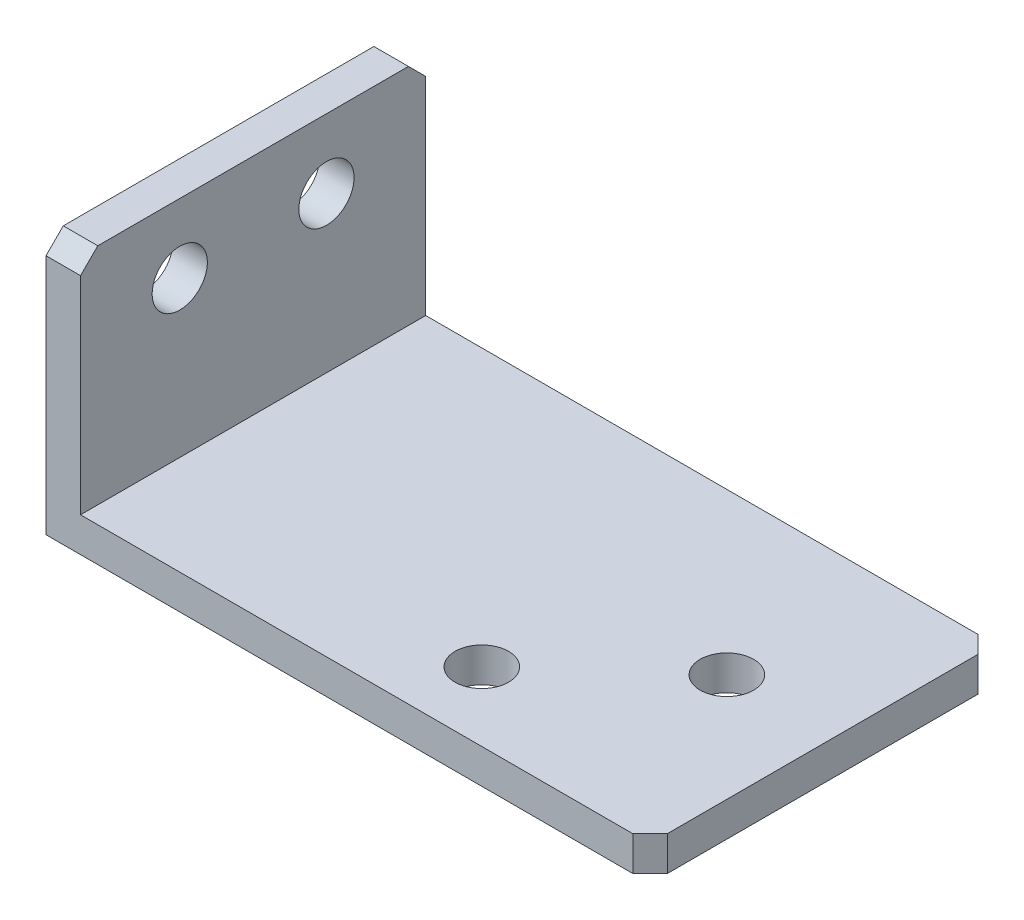
SolidWorks part; units mm, degrees
material "6063-T5"
ref_plane "Спереди" through (0, 0, 0) normal (0, 0, 1) x (1, 0, 0)
ref_plane "Сверху" through (0, 0, 0) normal (0, 1, 0) x (1, 0, 0)
ref_plane "Справа" through (0, 0, 0) normal (1, 0, 0) x (0, 0, -1)
sketch "Sketch1" plane through (0, 0, 0) normal (0, 0, 1) x (1, 0, 0)
  line L0 (0, 0) -> (35, 0)
  line L1 (35, 0) -> (35, 2)
  line L2 (35, 2) -> (2, 2)
  line L3 (2, 2) -> (2, 15)
  line L4 (2, 15) -> (0, 15)
  line L5 (0, 15) -> (0, 0)
  dimension "D1" = 35
  dimension "D2" = 15
  dimension "D4" = 2
extrude "Base" add sketch "Sketch1" along normal blind 20
sketch "Sketch5" plane through (0, 2, 0) normal (0, 1, 0) x (1, 0, 0)
  line L0 (0, -20) -> (0, 0) construction
  line L2 (35, -20) -> (2, -20) construction
  circle A0 centre (21.25, -16) radius 1.55
  circle A1 centre (28.75, -9.3) radius 1.55
  dimension "D3" = 3.1
  dimension "D1" = 4
  dimension "D2" = 6.7
  dimension "D4" = 7.5
  dimension "D5" = 21.25
extrude "CableChainSide" cut sketch "Sketch5" against normal through all
chamfer "Chamfer1" distance 1 angle 45 4 edges at (35, 1, 0) (1, 15, 0) (1, 15, 20) (35, 1, 20)
hole_wizard "Ø3.2 (3.2) Diameter Hole1" positions "Sketch6" profile "Sketch7" hole size "Ø3.2" standard "ANSI Metric" end condition through all
sketch "Sketch6" plane through (0, 0, 0) normal (-1, 0, 0) x (0, 0, 1)
  line L0 (20, 14) -> (20, 0) construction
  line L1 (20, 0) -> (0, 0) construction
  point P0 (5.75, 11)
  point P2 (14.25, 11)
  point P9 (0, 0)
  dimension "D1" = 8.5
  dimension "D2" = 5.75
  dimension "D3" = 11
sketch "Sketch7" plane through (0, 11, 5.75) normal (0, 1, 0) x (0, 0, 1)
  line L0 (0, 0) -> (0, 35)
  line L1 (0, 35) -> (1.6, 35)
  line L2 (1.6, 35) -> (1.6, 0)
  line L5 (1.6, 0) -> (0, 0)
  line L11 (0, -6.35) -> (0, 107.95) construction
  dimension "Thru Hole Dia." = 3.2
  dimension "Thru Hole Depth" = 35
